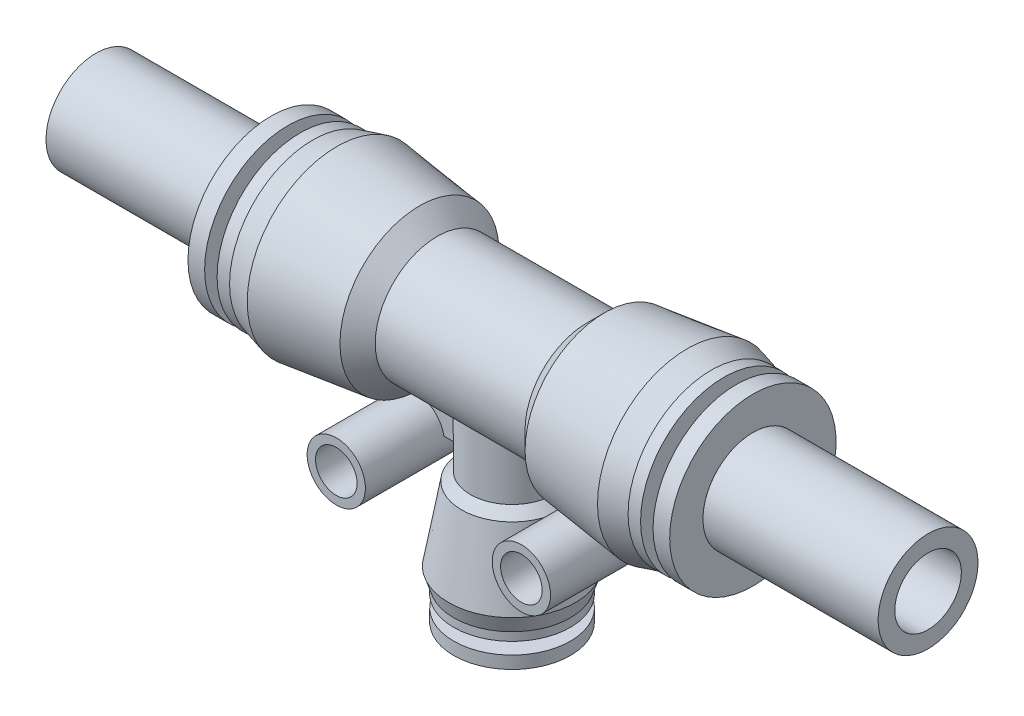
SolidWorks part; units mm, degrees
ref_plane "前视基准面" through (0, 0, 0) normal (0, 0, 1) x (1, 0, 0)
ref_plane "上视基准面" through (0, 0, 0) normal (0, 1, 0) x (1, 0, 0)
ref_plane "右视基准面" through (0, 0, 0) normal (1, 0, 0) x (0, 0, -1)
sketch "草图1" plane through (0, 0, 0) normal (0, 0, 1) x (1, 0, 0)
  line L0 (0, 0) -> (50.9152, 0) construction
  line L1 (0, -1.4364) -> (0, -23.0096) construction
  line L2 (-9, 0) -> (9, 0)
  line L3 (9, 0) -> (11.1213, 2.1213)
  line L4 (11.1213, 2.1213) -> (21.0468, 3.34)
  line L5 (21.0468, 3.34) -> (23.9446, 2.5636)
  line L6 (23.9446, 2.5636) -> (25.4446, 2.5636)
  line L7 (25.4446, 2.5636) -> (25.4446, -0.9332)
  line L8 (25.4446, -1.4364) -> (26.9446, -1.4364)
  line L9 (26.9446, -0.9332) -> (26.9446, 2.5636)
  line L10 (26.9446, 2.5636) -> (28.9446, 2.5636)
  line L11 (28.9446, 2.5636) -> (28.9446, -1.4364)
  line L12 (28.9446, -1.4364) -> (26.9446, -1.4364)
  line L13 (25.4446, -0.9332) -> (26.9446, -0.9332)
  line L14 (-35.5607, -7.4364) -> (35.5607, -7.4364) construction
  line L15 (25.4446, -1.4364) -> (-25.4446, -1.4364)
  line L17 (-25.4446, -0.9332) -> (-26.9446, -0.9332)
  line L18 (-28.9446, -1.4364) -> (-26.9446, -1.4364)
  line L19 (-28.9446, 2.5636) -> (-28.9446, -1.4364)
  line L20 (-26.9446, 2.5636) -> (-28.9446, 2.5636)
  line L21 (-26.9446, -0.9332) -> (-26.9446, 2.5636)
  line L22 (-25.4446, -1.4364) -> (-26.9446, -1.4364)
  line L23 (-25.4446, 2.5636) -> (-25.4446, -0.9332)
  line L24 (-23.9446, 2.5636) -> (-25.4446, 2.5636)
  line L25 (-21.0468, 3.34) -> (-23.9446, 2.5636)
  line L26 (-11.1213, 2.1213) -> (-21.0468, 3.34)
  line L27 (-9, 0) -> (-11.1213, 2.1213)
  point P20 (0, -7.4364)
  dimension "D1" = 9
  dimension "D2" = 3
  dimension "D3" = 10
  dimension "D4" = 3
  dimension "D5" = 1.5
  dimension "D6" = 1.5
  dimension "D7" = 2
  dimension "D8" = 4
  dimension "D9" = 6
revolve "旋转1" add sketch "草图1" angle 360 about L14
sketch "草图2" plane through (0, 0, 0) normal (0, 0, 1) x (1, 0, 0)
  line L0 (4, -14.8729) -> (5, -14.8729)
  line L1 (-9, -14.8729) -> (9, -14.8729) construction
  line L2 (5, -14.8729) -> (5, -19.8729)
  line L3 (5, -19.8729) -> (6.0607, -20.9335)
  line L4 (6.0607, -20.9335) -> (7.6235, -29.7968)
  line L5 (7.6235, -29.7968) -> (7.0015, -31.6976)
  line L6 (7.0015, -31.6976) -> (7.0015, -32.6976)
  line L7 (7.0015, -32.6976) -> (4.6372, -32.6976)
  line L8 (4.0049, -32.5553) -> (4.0049, -34.0553)
  line L9 (4.6372, -34.1265) -> (7.004, -34.1265)
  line L10 (7.004, -34.1265) -> (7.004, -35.6265)
  line L11 (7.004, -35.6265) -> (4.004, -35.6265)
  line L12 (4, -14.8729) -> (4, -29.6087)
  line L13 (4, -29.6087) -> (4.0049, -32.5553)
  line L14 (4, -14.8729) -> (5, -14.8729)
  line L15 (4.0049, -34.0553) -> (4.004, -35.6265)
  line L16 (4.6372, -32.6976) -> (4.6372, -34.1265)
  line L17 (0, 0) -> (0, -22.387) construction
  dimension "D2" = 5
  dimension "D3" = 1.5
  dimension "D4" = 9
  dimension "D5" = 2
  dimension "D6" = 1
  dimension "D7" = 1.5
  dimension "D8" = 1.5
  dimension "D9" = 3
  dimension "D10" = 3
  dimension "D11" = 3
  dimension "D12" = 1
revolve "旋转2" add sketch "草图2" angle 360 about L17 region at (5.3442, -26.7959, 0) other way angle 360
ref_plane "基准面1" through (0, -14.8729, 0) normal (0, 1, 0) x (1, 0, 0)
sketch "草图4" plane through (0, -14.8729, 0) normal (0, 1, 0) x (1, 0, 0)
  circle A0 centre (0, 0) radius 5
  circle A1 centre (0, 0) radius 4
extrude "凸台-拉伸1" add sketch "草图4" along normal up to surface up to face at (-9, -7.4364, 7.4364)
sketch "草图5" plane through (0, 0, 0) normal (0, 0, 1) x (1, 0, 0)
  line L0 (0, 0) -> (0, -41.7568) construction
  line L2 (11.1213, -16.9942) -> (21.0468, -18.2129) construction
  line L4 (5, -14.8729) -> (5, -19.8729)
  line L5 (55, -14.8729) -> (-55, -14.8729) construction
  line L7 (5, -19.8729) -> (5, -14.8729) construction
  line L9 (5, -19.8729) -> (7.6818, -19.8729)
  line L11 (11.1213, -17.0205) -> (9, -14.8729)
  line L12 (9, -14.8729) -> (11.1213, -16.9942) construction
  line L13 (9, -14.8729) -> (5, -14.8729)
  line L14 (-11.1213, -17.0205) -> (-9, -14.8729)
  line L15 (-9, -14.8729) -> (-5, -14.8729)
  line L16 (-5, -14.8729) -> (-5, -19.8729)
  line L17 (-5, -19.8729) -> (-7.6818, -19.8729)
  circle A0 centre (11.1213, -20.5205) radius 3.5
  circle A1 centre (11.1213, -20.5205) radius 2.5
  circle A2 centre (-11.1213, -20.5205) radius 2.5
  circle A3 centre (-11.1213, -20.5205) radius 3.5
  dimension "D1" = 7
extrude "凸台-拉伸5" add sketch "草图5" along normal mid plane 20 separate body contours A3 A2 | A0 A1 region at (8.9503, -17.9026, 0) region at (-8.9503, -17.9026, 0)
extrude "凸台-拉伸7" add sketch "草图5<9>" along normal mid plane 1 contours L14 A3 L17 L16 L15 | A0 L11 L13 L4 L9 region at (7.2239, -17.1075, 0) region at (-7.2239, -17.1075, 0)
sketch "草图5<9>" plane through (0, 0, 0) normal (0, 0, 1) x (1, 0, 0) same geometry as "草图5"
ref_plane "基准面2" through (0, -35.6265, 0) normal (0, -1, 0) x (-1, 0, 0)
sketch "草图8" plane through (0, -35.6265, 0) normal (0, -1, 0) x (-1, 0, 0)
  circle A0 centre (0, 0) radius 4
extrude "切除-拉伸1" cut sketch "草图8" against normal blind 27
ref_plane "基准面4" through (-28.9446, 0, 0) normal (-1, 0, 0) x (0, 0, 1)
sketch "草图11" plane through (-28.9446, 0, 0) normal (-1, 0, 0) x (0, 0, 1)
  circle A0 centre (0, -7.4364) radius 6
  circle A1 centre (0, -7.4364) radius 4
extrude "凸台-拉伸8" add sketch "草图11" along normal blind 21.06 separate body
ref_plane "基准面6" through (28.9446, 0, 0) normal (1, 0, 0) x (0, 0, -1)
sketch "草图13" plane through (28.9446, 0, 0) normal (1, 0, 0) x (0, 0, -1)
  circle A0 centre (0, -7.4364) radius 6
  circle A1 centre (0, -7.4364) radius 4
extrude "凸台-拉伸10" add sketch "草图13" along normal blind 21.05 separate body
